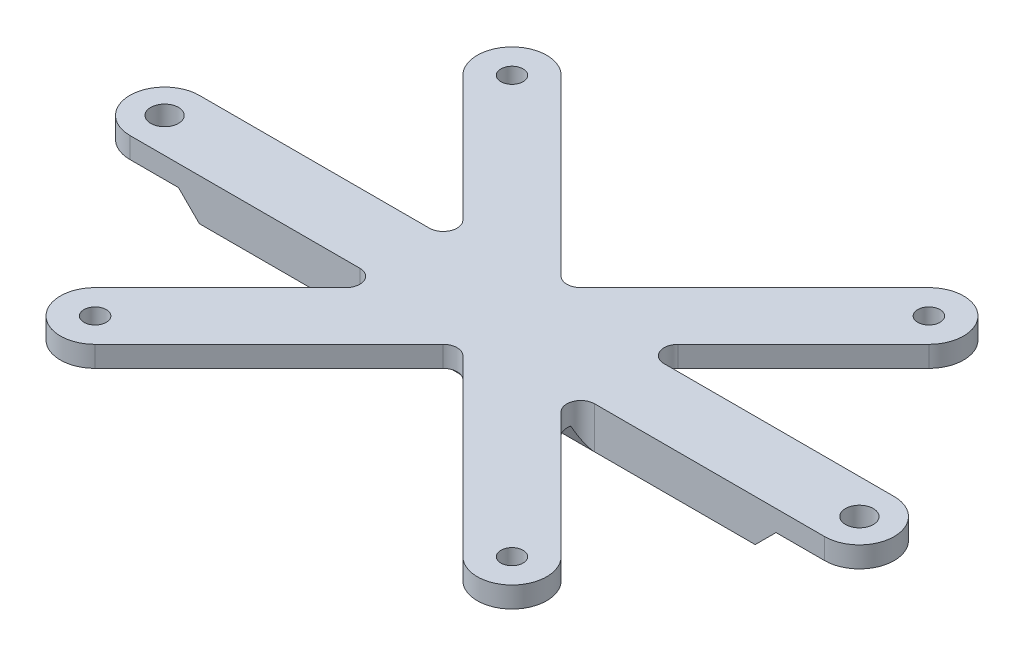
SolidWorks part; units mm, degrees
ref_plane "Front Plane" through (0, 0, 0) normal (0, 0, 1) x (1, 0, 0)
ref_plane "Top Plane" through (0, 0, 0) normal (0, 1, 0) x (1, 0, 0)
ref_plane "Right Plane" through (0, 0, 0) normal (1, 0, 0) x (0, 0, -1)
sketch "Sketch1" plane through (0, 0, 0) normal (0, 1, 0) x (1, 0, 0)
  line L5 (50, 5) -> (12.0711, 5)
  line L6 (26.4645, -33.5355) -> (0, -7.0711)
  line L7 (33.5355, 26.4645) -> (12.0711, 5)
  line L8 (33.5355, -26.4645) -> (12.0711, -5)
  line L9 (26.4645, 33.5355) -> (0, 7.0711)
  line L10 (50, -5) -> (12.0711, -5)
  line L11 (-50, -5) -> (-12.0711, -5)
  line L12 (-26.4645, 33.5355) -> (0, 7.0711)
  line L13 (-33.5355, -26.4645) -> (-12.0711, -5)
  line L14 (-33.5355, 26.4645) -> (-12.0711, 5)
  line L15 (-26.4645, -33.5355) -> (0, -7.0711)
  line L16 (-50, 5) -> (-12.0711, 5)
  circle A0 centre (50, 0) radius 2
  arc A1 (50, -5) -> (50, 5) centre (50, 0) ccw
  arc A2 (33.5355, 26.4645) -> (26.4645, 33.5355) centre (30, 30) ccw
  arc A3 (33.5355, -26.4645) -> (26.4645, -33.5355) centre (30, -30) cw
  arc A4 (-33.5355, -26.4645) -> (-26.4645, -33.5355) centre (-30, -30) ccw
  arc A5 (-33.5355, 26.4645) -> (-26.4645, 33.5355) centre (-30, 30) cw
  arc A6 (-50, -5) -> (-50, 5) centre (-50, 0) cw
  circle A7 centre (-50, 0) radius 2
  circle A8 centre (-30, 30) radius 1.6
  circle A9 centre (30, 30) radius 1.6
  circle A10 centre (-30, -30) radius 1.6
  circle A11 centre (30, -30) radius 1.6
extrude "Boss-Extrude1" add sketch "Sketch1" along normal blind 6
sketch "Sketch2" plane through (0, 0, 0) normal (0, -1, 0) x (1, 0, 0)
  line L0 (12.0711, -5) -> (-12.0711, -5)
  line L1 (-40, 0) -> (-40, 5)
  line L2 (-50, 5) -> (-12.0711, 5) construction
  line L3 (-40, 5) -> (-63.1219, 5)
  line L4 (-40, 0) -> (-40, -5)
  line L5 (-12.0711, -5) -> (-50, -5) construction
  line L6 (-40, -5) -> (-63.1219, -5)
  line L7 (-63.1219, -5) -> (-63.1219, 5)
  line L8 (-12.0711, -5) -> (-52.92, -33.6655)
  line L9 (63.1219, -5) -> (63.1219, 5)
  line L10 (40, -5) -> (63.1219, -5)
  line L11 (40, 0) -> (40, -5)
  line L12 (40, 5) -> (63.1219, 5)
  line L13 (40, 0) -> (40, 5)
  line L14 (-52.92, -33.6655) -> (13.7497, -59.4437)
  line L15 (13.7497, -59.4437) -> (60.2637, -26.8028)
  line L16 (60.2637, -26.8028) -> (12.0711, -5)
  line L17 (12.0711, 5) -> (-12.0711, 5)
  line L18 (-12.0711, 5) -> (-69.4674, 42.4271)
  line L19 (-69.4674, 42.4271) -> (19.137, 58.2057)
  line L20 (19.137, 58.2057) -> (60.2637, 41.0469)
  line L21 (60.2637, 41.0469) -> (12.0711, 5)
extrude "Cut-Extrude2" cut sketch "Sketch2" against normal blind 3
chamfer "Chamfer2" distance 3 angle 45 2 edges at (40, 3, 0) (-40, 3, 0)
chamfer "Chamfer3" distance 3 distance2 1.5 2 edges at (0, 3, 5) (0, 3, -5) first distance on face at (0, 3.5, 5) first distance on face at (0, 3.5, -5)
fillet "Fillet1" radius 2 6 edges at (0, 4.5, -7.0711) (0, 4.5, 7.0711) (-12.0711, 3, 5) (-12.0711, 3, -5) (12.0711, 3, -5) (12.0711, 3, 5)
